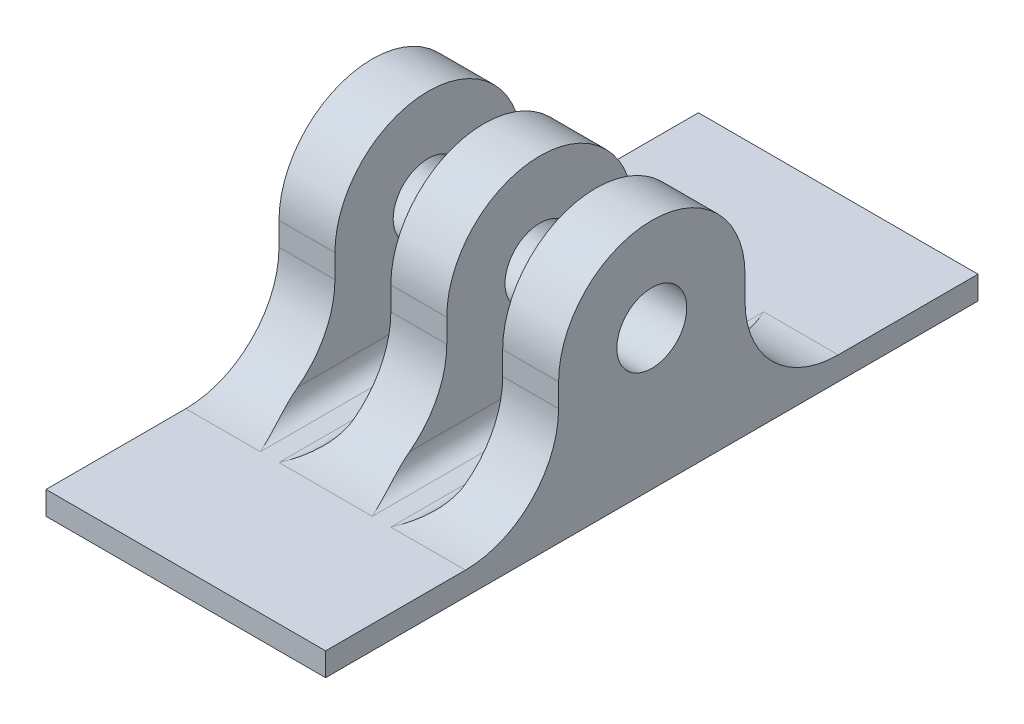
SolidWorks part; units mm, degrees
material "Plain Carbon Steel"
ref_plane "Front Plane" through (0, 0, 0) normal (0, 0, 1) x (1, 0, 0)
ref_plane "Top Plane" through (0, 0, 0) normal (0, 1, 0) x (1, 0, 0)
ref_plane "Right Plane" through (0, 0, 0) normal (1, 0, 0) x (0, 0, -1)
sketch "Sketch1" plane through (0, 0, 0) normal (1, 0, 0) x (0, 0, -1)
  line L0 (3.175, 31.75) -> (3.175, 15.875)
  line L1 (0, 0) -> (31.75, 0)
  line L2 (0, 0) -> (0, 12.7)
  line L3 (0, 12.7) -> (31.75, 12.7)
  line L4 (31.75, 0) -> (31.75, 12.7)
  line L5 (-3.175, 12.7) -> (34.925, 12.7)
  line L6 (-3.175, 12.7) -> (-3.175, 15.875)
  line L7 (-3.175, 15.875) -> (34.925, 15.875)
  line L8 (34.925, 12.7) -> (34.925, 15.875)
  line L9 (28.575, 31.75) -> (28.575, 15.875)
  line L10 (15.875, 31.75) -> (15.875, 15.875) construction
  line L11 (15.875, 15.875) -> (15.875, 0) construction
  arc A0 (28.575, 31.75) -> (3.175, 31.75) centre (15.875, 31.75) ccw
  circle A1 centre (15.875, 31.75) radius 4.7625
  dimension "D6" = 9.525
  dimension "D7" = 12.7
  dimension "D1" = 31.75
  dimension "D2" = 38.1
  dimension "D3" = 12.7
  dimension "D4" = 3.175
  dimension "D5" = 19.05
extrude "Boss-Extrude1" add sketch "Sketch1" along normal blind 38.1 contours L1 L4 L3 L2 | L5 L8 L7 L6 L3 | L9 A0 L0 L7 A1 region at (0, 44.0677, -15.875) region at (0, 14.2875, -15.875) region at (0, 6.35, -15.875)
sketch "Sketch3" plane through (0, 0, 0) normal (0, -1, 0) x (1, 0, 0)
  line L0 (0, 3.175) -> (38.1, -34.925) construction
  line L1 (38.1, 0) -> (0, 0) construction
  line L2 (3.175, -31.75) -> (34.925, -31.75)
  line L3 (3.175, -31.75) -> (3.175, 0)
  line L4 (3.175, 0) -> (34.925, 0)
  line L5 (34.925, -31.75) -> (34.925, 0)
  line L6 (3.175, -31.75) -> (34.925, 0) construction
  line L7 (3.175, 0) -> (34.925, -31.75) construction
  line L12 (0, 0) -> (0, -31.75)
  line L13 (0, -31.75) -> (38.1, -31.75)
  line L14 (38.1, -31.75) -> (38.1, 0)
  line L15 (38.1, 0) -> (0, 0)
  line L16 (0, 0) -> (0, -31.75)
  line L17 (0, -31.75) -> (38.1, -31.75)
  line L18 (38.1, -31.75) -> (38.1, 0)
  line L19 (38.1, 0) -> (0, 0)
  point P4 (19.05, -15.875)
  line M5 (0, 0) -> (0, -31.75)
  line M6 (0, -31.75) -> (38.1, -31.75)
  line M7 (38.1, -31.75) -> (38.1, 0)
  line M8 (38.1, 0) -> (0, 0)
  dimension "D1" = 0
extrude "Cut-Extrude1" cut sketch "Sketch3" against normal up to surface (12.7 mm away) contours L3 M6 M8 M5 | L5 M6 M7 M8 region at (1.5875, 0, -15.875) region at (36.5125, 0, -15.875) up to face at (19.05, 12.7, 1.5875)
sketch "Sketch4" plane through (0, 15.875, 0) normal (0, 1, 0) x (1, 0, 0)
  line L0 (38.1, -3.175) -> (0, -3.175) construction
  line L1 (0, 34.925) -> (7.62, 34.925)
  line L2 (0, 34.925) -> (0, -3.175)
  line L3 (0, -3.175) -> (7.62, -3.175)
  line L4 (7.62, 34.925) -> (7.62, -3.175)
  line L6 (7.62, 34.925) -> (15.24, 34.925)
  line L7 (7.62, 34.925) -> (7.62, -3.175)
  line L8 (7.62, -3.175) -> (15.24, -3.175)
  line L9 (15.24, 34.925) -> (15.24, -3.175)
  line L10 (15.24, 34.925) -> (22.86, 34.925)
  line L11 (15.24, 34.925) -> (15.24, -3.175)
  line L12 (15.24, -3.175) -> (22.86, -3.175)
  line L13 (22.86, 34.925) -> (22.86, -3.175)
  line L14 (22.86, 34.925) -> (30.48, 34.925)
  line L15 (22.86, 34.925) -> (22.86, -3.175)
  line L16 (22.86, -3.175) -> (30.48, -3.175)
  line L17 (30.48, 34.925) -> (30.48, -3.175)
  line L18 (38.1, 34.925) -> (30.48, 34.925)
  line L19 (38.1, 34.925) -> (38.1, -3.175)
  line L20 (38.1, -3.175) -> (30.48, -3.175)
  line L21 (30.48, 34.925) -> (30.48, -3.175)
  line M2 (0, 28.575) -> (38.1, 28.575)
  line M4 (38.1, 34.925) -> (0, 34.925)
extrude "Cut-Extrude2" cut sketch "Sketch4" along normal through all contours L9 L4 L8 M2 | L17 L13 L16 M2 | L9 L4 M4 M2 | L17 L13 M4 M2 region at (11.43, 15.875, -31.75) region at (11.43, 15.875, -12.7) region at (26.67, 15.875, -31.75) region at (26.67, 15.875, -12.7)
sketch "Sketch6" plane through (0, 0, 0) normal (0, -1, 0) x (1, 0, 0)
  line L4 (34.925, -31.75) -> (34.925, 0)
  line L5 (34.925, 0) -> (3.175, 0)
  line L6 (3.175, 0) -> (3.175, -31.75)
  line L7 (3.175, -31.75) -> (34.925, -31.75)
  line L8 (34.925, -31.75) -> (34.925, 0)
  line L9 (34.925, 0) -> (3.175, 0)
  line L10 (3.175, 0) -> (3.175, -31.75)
  line L11 (3.175, -31.75) -> (34.925, -31.75)
  dimension "D1" = 0
extrude "Cut-Extrude3" cut sketch "Sketch6" against normal up to surface (12.7 mm away) up to face at (19.05, 12.7, -15.875)
sketch "Sketch7" plane through (0, 12.7, 0) normal (0, -1, 0) x (1, 0, 0)
  line L0 (0, -3.175) -> (0, -28.575) construction
  line L1 (0, -60.325) -> (38.1, -60.325)
  line L2 (0, -60.325) -> (0, 28.575)
  line L3 (0, 28.575) -> (38.1, 28.575)
  line L4 (38.1, -60.325) -> (38.1, 28.575)
  line L5 (38.1, 3.175) -> (38.1, -3.175) construction
  line L6 (38.1, 3.175) -> (0, 3.175) construction
  line L7 (38.1, -34.925) -> (0, -34.925) construction
  dimension "D1" = 25.4
  dimension "D2" = 25.4
extrude "Boss-Extrude2" add sketch "Sketch7" against normal up to surface (3.175 mm away) up to face at (19.05, 15.875, -15.875)
fillet "Fillet1" radius 2.54 4 edges at (30.48, 15.875, -15.875) (22.86, 15.875, -15.875) (15.24, 15.875, -15.875) (7.62, 15.875, -15.875)
fillet "Fillet2" radius 12.7 6 edges at (33.02, 15.875, -28.575) (19.05, 15.875, -28.575) (5.08, 15.875, -28.575) (33.02, 15.875, -3.175) (19.05, 15.875, -3.175) (5.08, 15.875, -3.175)
ref_plane "Plane1" through (0, 0, -15.875) normal (0, 0, 1) x (1, 0, 0)
